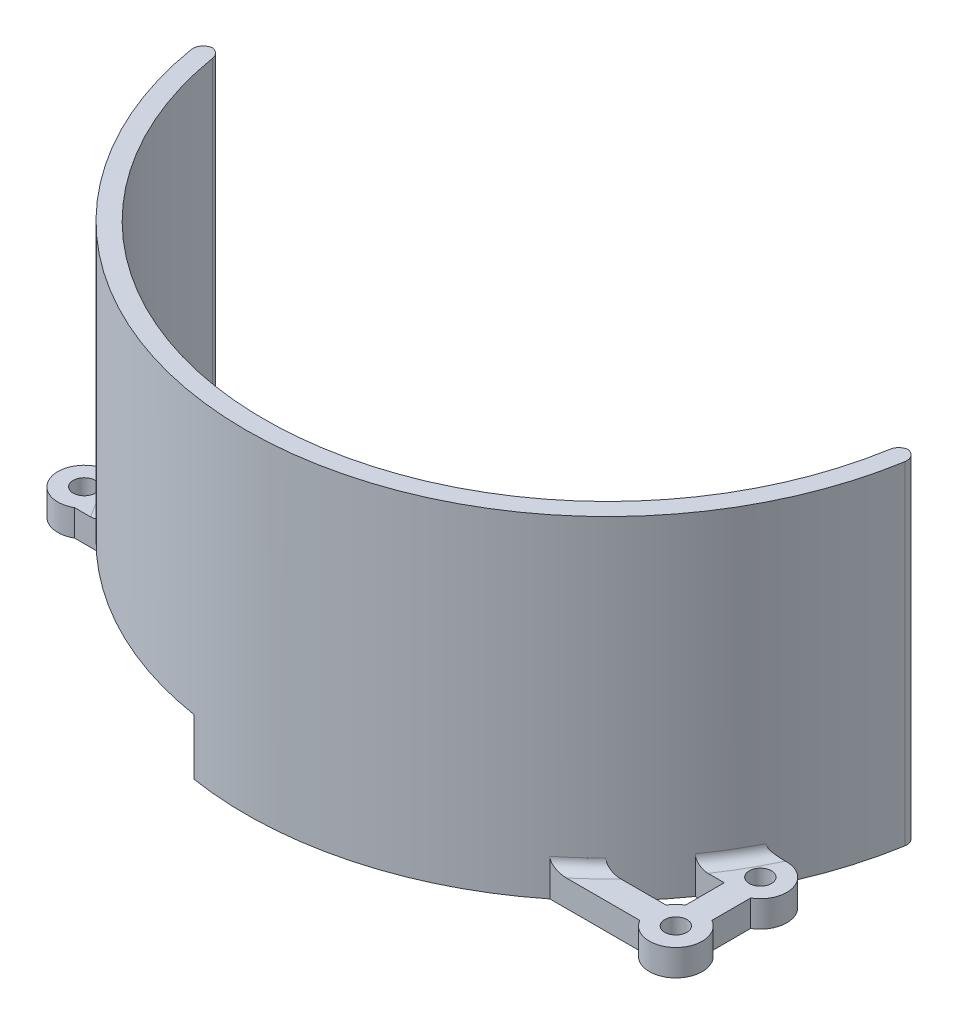
SolidWorks part; units mm, degrees
ref_plane "Front" through (0, 0, 0) normal (0, 0, 1) x (1, 0, 0)
ref_plane "Top" through (0, 0, 0) normal (0, 1, 0) x (1, 0, 0)
ref_plane "Right" through (0, 0, 0) normal (1, 0, 0) x (0, 0, -1)
sketch "Sketch1" plane through (0, 0, 0) normal (0, 1, 0) x (1, 0, 0)
  line L2 (66.4997, -46.7697) -> (66.4997, -39.4303)
  line L3 (59.6699, -48.6) -> (48.2731, -48.6)
  line L4 (59.6699, -53.6) -> (42.6531, -53.6)
  line L7 (0, 0) -> (0, -50000) construction
  line L8 (61.5003, -39.4303) -> (56.0134, -39.4303)
  line L11 (61.5003, -39.4303) -> (61.5003, -46.7697)
  line L14 (-56.0134, -39.4303) -> (-61.5003, -39.4303)
  line L16 (67.9087, -8.9812) -> (64.3765, -8.9812)
  line L17 (-64.3765, -8.9812) -> (-67.9087, -8.9812)
  arc A0 (-64.3765, -8.9812) -> (64.3765, -8.9812) centre (0, 0) ccw
  circle A31 centre (64, -51.1) radius 2.1
  arc A32 (59.6699, -53.6) -> (66.4997, -46.7697) centre (64, -51.1) ccw
  arc A33 (61.5003, -46.7697) -> (59.6699, -48.6) centre (64, -51.1) ccw
  circle A38 centre (-64, -35.1) radius 2.1
  arc A39 (-61.0531, -31.0607) -> (-61.5003, -39.4303) centre (-64, -35.1) ccw
  circle A40 centre (64, -35.1) radius 2.1
  arc A41 (66.4997, -39.4303) -> (61.0531, -31.0607) centre (64, -35.1) ccw
  arc A42 (61.0531, -31.0607) -> (67.9087, -8.9812) centre (0, 0) ccw
  arc A44 (48.2731, -48.6) -> (56.0134, -39.4303) centre (0, 0) ccw
  arc A45 (-67.9087, -8.9812) -> (-61.0531, -31.0607) centre (0, 0) ccw
  arc A46 (-56.0134, -39.4303) -> (42.6531, -53.6) centre (0, 0) ccw
  point P6 (0, 0)
  point P45 (0, -32)
extrude "Boss-Extrude1" add sketch "Sketch1" along normal blind 63
sketch "Sketch2" plane through (0, 63, 0) normal (0, 1, 0) x (1, 0, 0)
  circle A0 centre (0, 0) radius 68.5
  circle A1 centre (0, 0) radius 90.0412
extrude "Cut-Extrude1" cut sketch "Sketch2" against normal blind 58
ref_plane "Plane1" through (0, 63, 68.5) normal (0, 0, 1) x (1, 0, 0)
sketch "Sketch3" plane through (0, 63, 68.5) normal (0, 0, 1) x (1, 0, 0)
  line L7 (-56.5639, -67.6084) -> (-10.602, -67.6084)
  line L8 (-56.5639, -67.6084) -> (-56.5639, -52.3916)
  line L9 (-56.5639, -52.3916) -> (-10.602, -52.3916)
  line L10 (-10.602, -67.6084) -> (-10.602, -52.3916)
  line L11 (-56.5639, -67.6084) -> (-10.602, -52.3916) construction
  line L12 (-56.5639, -52.3916) -> (-10.602, -67.6084) construction
  point P5 (-33.583, -60)
extrude "Cut-Extrude2" cut sketch "Sketch3" against normal blind 55
fillet "Fillet1" radius 2 3 edges at (58.6827, 5, 35.3355) (45.5318, 5, 51.1772) (-58.9304, 5, 34.9208)
fillet "Fillet2" radius 2 4 edges at (-67.9087, 31.5, 8.9812) (-64.3765, 31.5, 8.9812) (64.3765, 31.5, 8.9812) (67.9087, 31.5, 8.9812)
